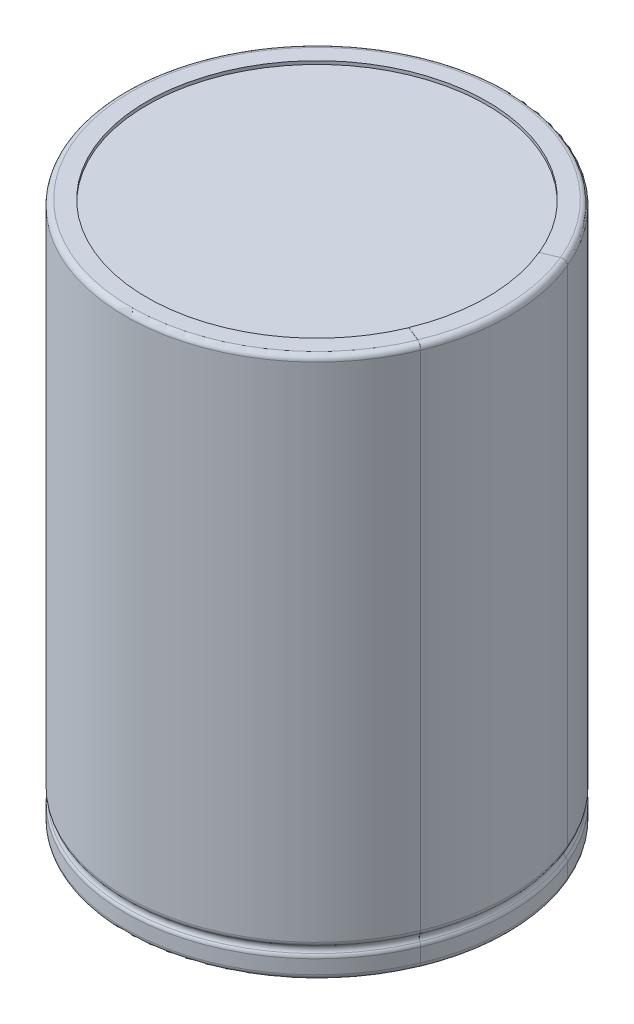
SolidWorks part; units mm, degrees
material "Cap"
ref_plane "Front Plane" through (0, 0, 0) normal (0, 0, 1) x (1, 0, 0)
ref_plane "Top Plane" through (0, 0, 0) normal (0, 1, 0) x (1, 0, 0)
ref_plane "Right Plane" through (0, 0, 0) normal (1, 0, 0) x (0, 0, -1)
sketch "Sketch1" plane through (0, 0, 0) normal (0, 0, 1) x (1, 0, 0)
  line L0 (0, 0.3) -> (0, 49.7)
  line L1 (0, 49.7) -> (15.7, 49.7)
  line L2 (15.7, 49.7) -> (15.7, 50)
  line L3 (15.7, 50) -> (17.2, 50)
  line L4 (17.7, 49.5) -> (17.7, 3.0945)
  line L5 (17.7, 1.7716) -> (17.7, 0.5)
  line L6 (17.2, 0) -> (15.7, 0)
  line L7 (0, 0) -> (0, -8.1899) construction
  line L8 (0, 0.3) -> (15.7, 0.3)
  line L9 (15.7, 0.3) -> (15.7, 0)
  line L10 (0, 25) -> (1.9584, 25) construction
  arc A0 (17.575, 2.7637) -> (17.575, 2.1023) centre (17.95, 2.433) ccw
  arc A1 (17.7, 49.5) -> (17.2, 50) centre (17.2, 49.5) ccw
  arc A2 (17.7, 3.0945) -> (17.575, 2.7637) centre (17.2, 3.0945) cw
  arc A3 (17.7, 1.7716) -> (17.575, 2.1023) centre (17.2, 1.7716) ccw
  arc A4 (17.2, 0) -> (17.7, 0.5) centre (17.2, 0.5) ccw
  point P13 (17.7, 50)
  point P18 (17.7, 2)
  point P21 (17.7, 0)
  dimension "D3" = 0.5
  dimension "D5" = 0.5
  dimension "D1" = 0.3
  dimension "D2" = 2
  dimension "D4" = 2
  dimension "D" = 35.4
  dimension "L" = 50
  dimension "D9" = 0.25
revolve "Revolve1" add sketch "Sketch1" angle 360 about L7 reverse direction yes
sketch "Sketch2" plane through (0, 0.3, 0) normal (0, -1, 0) x (1, 0, 0)
  line L0 (-5, 0) -> (0, 0) construction
  line L1 (0, 0) -> (0, 0.7452) construction
  circle A0 centre (-5, 0) radius 0.5
  circle A1 centre (5, 0) radius 0.5
  dimension "d" = 1
  dimension "S" = 10
extrude "Extrude1" add sketch "Sketch2" along normal blind 3
sketch "Sketch3" plane through (0, 0, 0) normal (0, 0, 1) x (1, 0, 0)
  line L10 (15.69, 50.01) -> (15.69, -0.01)
  line L18 (-0.01, 49.71) -> (-0.01, 0.29)
  line L19 (15.69, 49.71) -> (-0.01, 49.71)
  line L20 (15.69, 50.01) -> (15.69, 49.71)
  line L21 (17.2, 50.01) -> (15.69, 50.01)
  line L22 (17.71, 3.0945) -> (17.71, 49.5)
  line L23 (17.71, 0.5) -> (17.71, 1.7716)
  line L24 (15.69, -0.01) -> (17.2, -0.01)
  line L25 (15.69, 0.29) -> (15.69, -0.01)
  line L26 (-0.01, 0.29) -> (15.69, 0.29)
  line L27 (-0.01, 49.71) -> (-0.01, 0.29) construction
  line L28 (15.69, 49.71) -> (-0.01, 49.71) construction
  line L29 (15.69, 50.01) -> (15.69, 49.71) construction
  line L30 (17.2, 50.01) -> (15.69, 50.01)
  line L31 (17.71, 3.0945) -> (17.71, 49.5)
  line L32 (17.71, 0.5) -> (17.71, 1.7716)
  line L33 (15.69, -0.01) -> (17.2, -0.01)
  line L34 (15.69, 0.29) -> (15.69, -0.01) construction
  line L35 (-0.01, 0.29) -> (15.69, 0.29) construction
  arc A10 (17.71, 49.5) -> (17.2, 50.01) centre (17.2, 49.5) ccw
  arc A11 (17.5825, 2.7571) -> (17.71, 3.0945) centre (17.2, 3.0945) ccw
  arc A12 (17.5825, 2.7571) -> (17.5825, 2.1089) centre (17.95, 2.433) ccw
  arc A13 (17.71, 1.7716) -> (17.5825, 2.1089) centre (17.2, 1.7716) ccw
  arc A14 (17.2, -0.01) -> (17.71, 0.5) centre (17.2, 0.5) ccw
  arc A15 (17.71, 49.5) -> (17.2, 50.01) centre (17.2, 49.5) ccw
  arc A16 (17.5825, 2.7571) -> (17.71, 3.0945) centre (17.2, 3.0945) ccw
  arc A17 (17.5825, 2.7571) -> (17.5825, 2.1089) centre (17.95, 2.433) ccw
  arc A18 (17.71, 1.7716) -> (17.5825, 2.1089) centre (17.2, 1.7716) ccw
  arc A19 (17.2, -0.01) -> (17.71, 0.5) centre (17.2, 0.5) ccw
  dimension "D1" = 0.01
revolve "Revolve2" add sketch "Sketch3" angle 45 mid plane about L27
